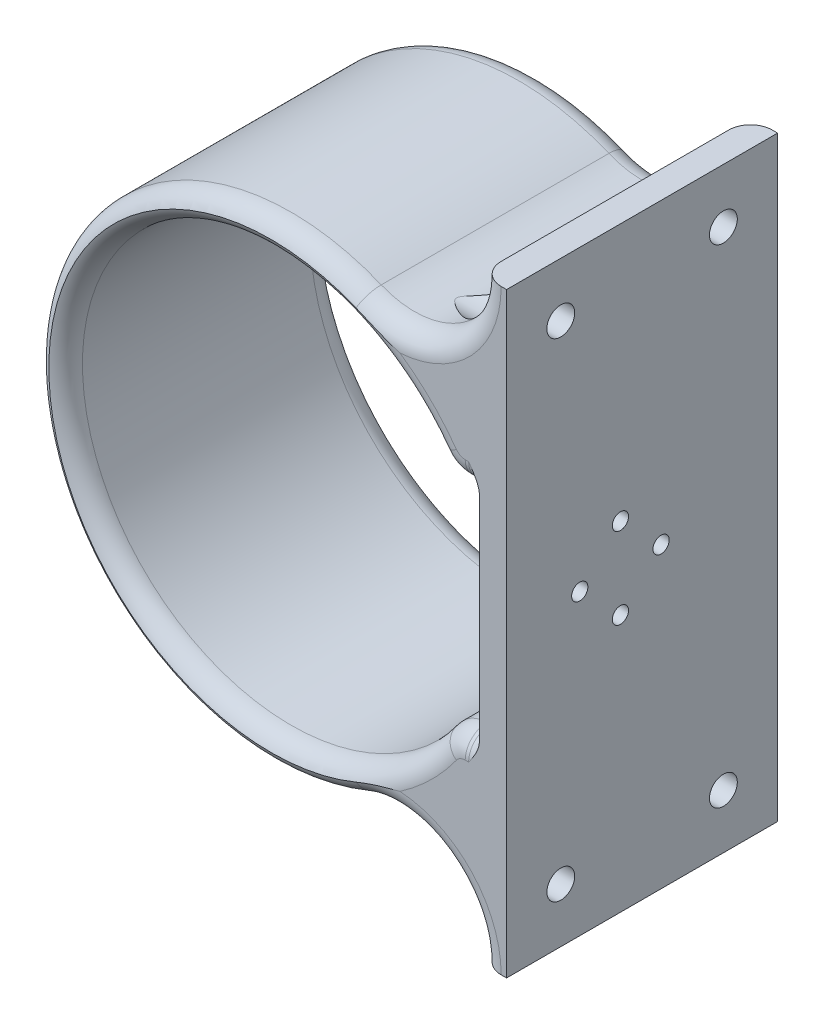
SolidWorks part; units mm, degrees
material "Markforged Onyx"
ref_plane "Front Plane" through (0, 0, 0) normal (0, 0, 1) x (1, 0, 0)
ref_plane "Top Plane" through (0, 0, 0) normal (0, 1, 0) x (1, 0, 0)
ref_plane "Right Plane" through (0, 0, 0) normal (1, 0, 0) x (0, 0, -1)
sketch "Sketch1" plane through (0, 0, 0) normal (0, 0, 1) x (1, 0, 0)
  line L0 (0, 0) -> (55.5625, 0) construction
  line L1 (45.21, 31.75) -> (55.5625, 31.75)
  line L2 (0, 55.245) -> (0, -55.245) construction
  line L3 (55.5625, 31.75) -> (55.5625, -31.75)
  line L4 (55.5625, -31.75) -> (45.21, -31.75)
  line L6 (41.7799, -25.4) -> (49.2125, -25.4)
  line L7 (49.2125, -25.4) -> (49.2125, 25.4)
  line L8 (49.2125, 25.4) -> (41.7799, 25.4)
  line L10 (55.5625, -69.85) -> (49.2125, -69.85)
  line L11 (55.5625, -69.85) -> (55.5625, 69.85)
  line L12 (55.5625, 69.85) -> (49.2125, 69.85)
  line L13 (49.2125, -69.85) -> (49.2125, 69.85)
  line L14 (55.5625, -69.85) -> (49.2125, 69.85) construction
  line L15 (55.5625, 69.85) -> (49.2125, -69.85) construction
  arc A0 (45.21, 31.75) -> (45.21, -31.75) centre (0, 0) ccw
  arc A1 (41.7799, 25.4) -> (41.7799, -25.4) centre (0, 0) ccw
  circle A8 centre (0, 0) radius 48.895 construction
  circle A9 centre (0, 0) radius 55.245 construction
  point P1 (52.3875, 0)
  point P4 (46.1513, 14.1099)
  point P24 (40.0787, 12.2533)
  dimension "D1" = 110.49
  dimension "D4" = 6.35
  dimension "D3" = 6.35
  dimension "D5" = 6.35
  dimension "D6" = 63.5
  dimension "D7" = 55.5625
  dimension "D8" = 38.1
  dimension "D2" = 6.35
extrude "Boss-Extrude1" add sketch "Sketch1" along normal blind 63.5 contours A0 | A1 A0 | L13 L10 L11 L4 | L13 L1 L11 L12 | L13 L4 L3 L1 L7 region at (47.2113, 30.2295, 0) region at (52.3875, 50.8, 0) region at (52.3875, 0, 0) region at (52.3875, -50.8, 0)
sketch3d "3DSketch1" plane through (0, 0, 0) normal (0, 0, 1) x (1, 0, 0)
  dimension "D1" = 71.12
ref_plane "Plane1" through (0, 50.8, 0) normal (0, 1, 0) x (1, 0, 0)
fillet "Fillet1" radius 33.02 2 edges at (45.21, 31.75, 31.75) (45.21, -31.75, 31.75)
fillet "Fillet2" radius 7.62 2 edges at (41.7799, 25.4, 31.75) (41.7799, -25.4, 31.75)
fillet "Fillet3" radius 20.32 2 edges at (49.2125, 31.75, 31.75) (49.2125, -31.75, 31.75)
sketch "Sketch3" plane through (55.5625, 0, 0) normal (1, 0, 0) x (0, 0, -1)
  line L0 (-63.5, -57.15) -> (0, -57.15) construction
  line L1 (-63.5, 69.85) -> (-63.5, -69.85) construction
  line L2 (0, 69.85) -> (0, -69.85) construction
  line L3 (-63.5, -69.85) -> (0, -69.85) construction
  line L5 (35.6493, 0) -> (-35.6493, 0) construction
  line L6 (-63.5, 57.15) -> (0, 57.15) construction
  circle A0 centre (-50.8, -57.15) radius 3.2639
  circle A1 centre (-31.75, -57.15) radius 3.2639 construction
  circle A2 centre (-12.7, -57.15) radius 3.2639
  circle A3 centre (-12.7, 57.15) radius 3.2639
  circle A4 centre (-31.75, 57.15) radius 3.2639 construction
  circle A5 centre (-50.8, 57.15) radius 3.2639
  circle A6 centre (-50.8, -57.15) radius 3.5179
  circle A7 centre (-31.75, -57.15) radius 3.5179 construction
  circle A8 centre (-12.7, -57.15) radius 3.5179
  circle A9 centre (-50.8, 57.15) radius 3.5179
  circle A10 centre (-31.75, 57.15) radius 3.5179 construction
  circle A11 centre (-12.7, 57.15) radius 3.5179
  point P6 (-31.75, -57.15)
  dimension "D3" = 6.5278
  dimension "D1" = 12.7
  dimension "D2" = 19.05
  dimension "D4" = 19.05
  dimension "D5" = 0.254
extrude "Cut-Extrude1" cut sketch "Sketch3" against normal blind 33.02 contours A2 | A0 | A4 | A3 | A1 | A5 region at (55.5625, -57.15, 50.8) region at (55.5625, -57.15, 12.7) region at (55.5625, 57.15, 12.7)
fillet "Fillet4" radius 5.08 10 edges at (47.5389, 25.4, 0) (42.3912, 26.2381, 0) (47.5389, -25.4, 0) (42.3912, -26.2381, 0) (49.2125, 69.8366, 0) (40.1847, 52.9299, 0) (49.2125, -69.8366, 0) (40.1847, -52.9299, 0) (-48.895, 0, 0) (-55.245, 0, 0)
fillet "Fillet5" radius 5.08 10 edges at (47.5389, 25.4, 63.5) (42.3912, 26.2381, 63.5) (47.5389, -25.4, 63.5) (42.3912, -26.2381, 63.5) (49.2125, 69.8366, 63.5) (40.1847, 52.9299, 63.5) (49.2125, -69.8366, 63.5) (40.1847, -52.9299, 63.5) (-48.895, 0, 63.5) (-55.245, 0, 63.5)
fillet "Fillet6" radius 2.54 6 edges at (49.2125, 26.8879, 62.0121) (49.2125, 26.8879, 1.4879) (49.2125, -26.8879, 62.0121) (49.2125, -26.8879, 1.4879) (49.2125, 25.4, 31.75) (49.2125, -25.4, 31.75)
sketch "Sketch6" plane through (55.5625, 0, 0) normal (1, 0, 0) x (0, 0, -1)
  line L0 (-63.5, 0) -> (0, 0) construction
  line L1 (-63.5, 69.85) -> (-63.5, -69.85) construction
  line L2 (0, 69.85) -> (0, -69.85) construction
  circle A0 centre (-36.83, 0) radius 9.525 construction
  circle A1 centre (-46.355, 0) radius 1.905
  circle A2 centre (-36.83, 9.525) radius 1.905
  circle A3 centre (-27.305, 0) radius 1.905
  circle A4 centre (-36.83, -9.525) radius 1.905
  point P19 (-36.83, 0)
  dimension "D1" = 19.05
  dimension "D2" = 3.81
  dimension "D4" = 26.67
  dimension "D3" = 4
extrude "Cut-Extrude2" cut sketch "Sketch6" against normal up to surface (104.4575 mm away) up to face at (-4.6069, 0, 31.75)
ref_plane "Plane2" through (49.2125, 0, 0) normal (1, 0, 0) x (0, 0, -1)
sketch "Sketch8" plane through (49.2125, 0, 0) normal (1, 0, 0) x (0, 0, -1)
  circle A0 centre (-12.7, -57.15) radius 3.2639 construction
  circle A2 centre (-50.8, -57.15) radius 3.2639 construction
  circle A3 centre (-12.7, 57.15) radius 3.2639 construction
  circle A5 centre (-50.8, 57.15) radius 3.2639 construction
  circle A6 centre (-12.7, -57.15) radius 3.2639
  circle A8 centre (-50.8, -57.15) radius 3.2639
  circle A9 centre (-12.7, 57.15) radius 3.2639
  circle A11 centre (-50.8, 57.15) radius 3.2639
  circle A12 centre (-50.8, 57.15) radius 7.5184
  circle A14 centre (-12.7, 57.15) radius 7.5184
  circle A15 centre (-50.8, -57.15) radius 7.5184
  circle A17 centre (-12.7, -57.15) radius 7.5184
  dimension "D1" = 4.2545
extrude "Cut-Extrude3" cut sketch "Sketch8" against normal blind 20.32 contours A12 A11 | A14 A9 | A17 A6 | A15 A8 region at (49.2125, 57.15, 58.1057) region at (49.2125, 57.15, 20.0057) region at (49.2125, -57.15, 58.1057) region at (49.2125, -57.15, 20.0057)
equation "\"3.5inn\"=3.75"
